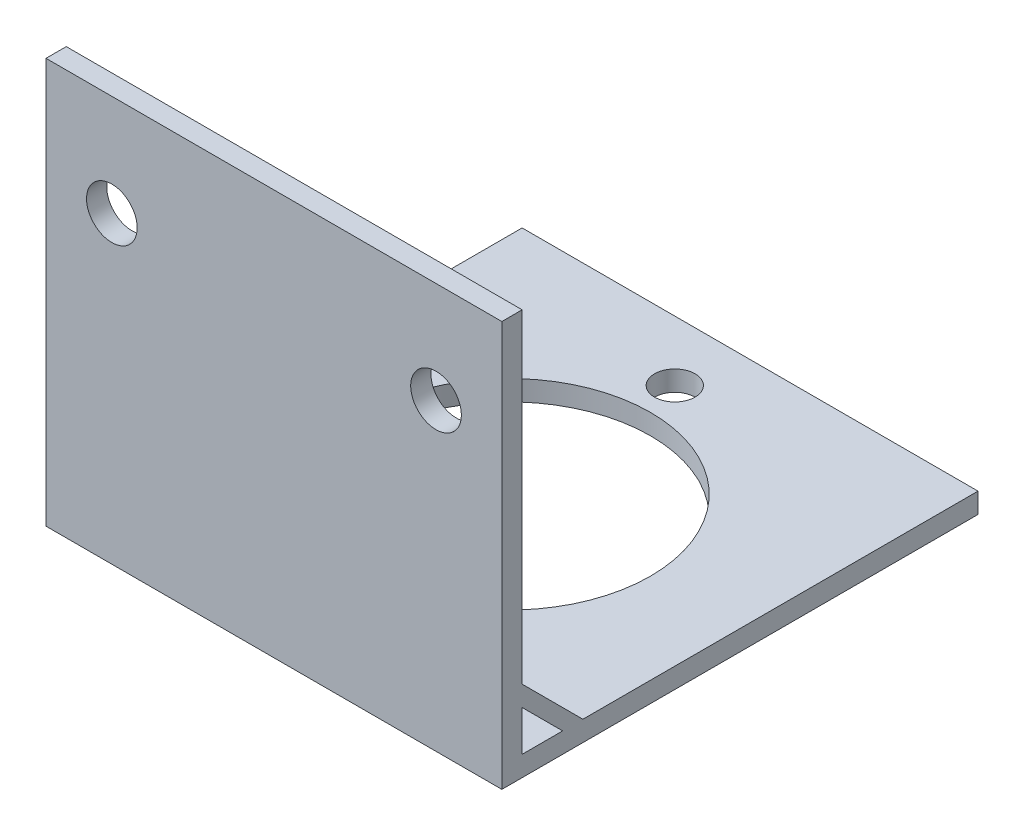
SolidWorks part; units mm, degrees
ref_plane "Front Plane" through (0, 0, 0) normal (0, 0, 1) x (1, 0, 0)
ref_plane "Top Plane" through (0, 0, 0) normal (0, 1, 0) x (1, 0, 0)
ref_plane "Right Plane" through (0, 0, 0) normal (1, 0, 0) x (0, 0, -1)
sketch "Sketch7" plane through (0, 0, 0) normal (0, 1, 0) x (1, 0, 0)
  line L0 (28.2563, -140.551) -> (-16.7437, -140.551)
  line L1 (28.2563, -95.551) -> (-16.7437, -95.551)
  line L2 (28.2563, -95.551) -> (28.2563, -142.551)
  line L3 (28.2563, -142.551) -> (-16.7437, -142.551)
  line L4 (-16.7437, -95.551) -> (-16.7437, -142.551)
  line L5 (28.2563, -95.551) -> (-16.7437, -142.551) construction
  line L6 (28.2563, -142.551) -> (-16.7437, -95.551) construction
  circle A0 centre (12.3619, -118.9637) radius 4.5
  circle A1 centre (5.362, -118.9853) radius 14
  circle A2 centre (4.2594, -101.4853) radius 2
  circle A3 centre (4.2594, -136.4853) radius 2
  circle A4 centre (12.3619, -118.9637) radius 3
  point P0 (5.7563, -119.051)
  dimension "D1" = 47
  dimension "D2" = 45
  dimension "D3" = 2
extrude "Boss-Extrude5" add sketch "Sketch7" along normal blind 2 separate body contours L1 L4 L0 L2 A3 A2 A1 region at (5.7563, 0, 139.9146)
extrude "Boss-Extrude6" add sketch "Sketch7<3>" along normal blind 40 contours L0 L4 L3 L2 region at (5.7563, 0, 141.551)
sketch "Sketch7<3>" plane through (0, 0, 0) normal (0, 1, 0) x (1, 0, 0) same geometry as "Sketch7"
sketch "Sketch8" plane through (-16.7437, 0, 0) normal (-1, 0, 0) x (0, 0, 1)
  line L0 (140.551, 6) -> (136.551, 2)
  line L1 (140.551, 40) -> (140.551, 2) construction
  line L2 (95.551, 2) -> (140.551, 2) construction
  line L3 (134.551, 2) -> (140.551, 8)
  line L4 (140.551, 8) -> (140.551, 6)
  line L5 (136.551, 2) -> (134.551, 2)
  dimension "D1" = 4
  dimension "D2" = 4
  dimension "D3" = 6
  dimension "D4" = 6
extrude "Boss-Extrude7" add sketch "Sketch8" against normal blind 2
ref_plane "Plane2" through (5.7563, 0, 0) normal (-1, 0, 0) x (0, 0, 1)
mirror "Mirror2" about plane through (5.7563, 0, 0) normal (-1, 0, 0) of "Boss-Extrude7"
sketch "Sketch9" plane through (0, 0, 142.551) normal (0, 0, 1) x (1, 0, 0)
  line L0 (5.7563, 22) -> (5.7563, -22) construction
  line L1 (-15.2437, 37) -> (26.7563, 37)
  line L2 (-15.2437, 37) -> (-15.2437, 23)
  line L3 (-15.2437, 23) -> (26.7563, 23)
  line L4 (26.7563, 37) -> (26.7563, 23)
  line L5 (-15.2437, 37) -> (26.7563, 23) construction
  line L6 (-15.2437, 23) -> (26.7563, 37) construction
  line L7 (28.2563, 0) -> (-16.7437, 0) construction
  point P0 (5.7563, 30)
  dimension "D1" = 23
  dimension "D2" = 14
  dimension "D3" = 42
sketch "Sketch10" plane through (0, 0, 142.551) normal (0, 0, 1) x (1, 0, 0)
  line L0 (26.7563, 37) -> (26.7563, 23) construction
  line L1 (-15.2437, 37) -> (26.7563, 37) construction
  line L2 (-15.2437, 37) -> (-15.2437, 23) construction
  circle A0 centre (21.7563, 30) radius 2.5
  circle A1 centre (-10.2437, 30) radius 2.5
  dimension "D1" = 5
  dimension "D2" = 5
  dimension "D4" = 5
  dimension "D3" = 7
  dimension "D5" = 7
  dimension "D6" = 5
extrude "Cut-Extrude2" cut sketch "Sketch10" against normal blind 2
